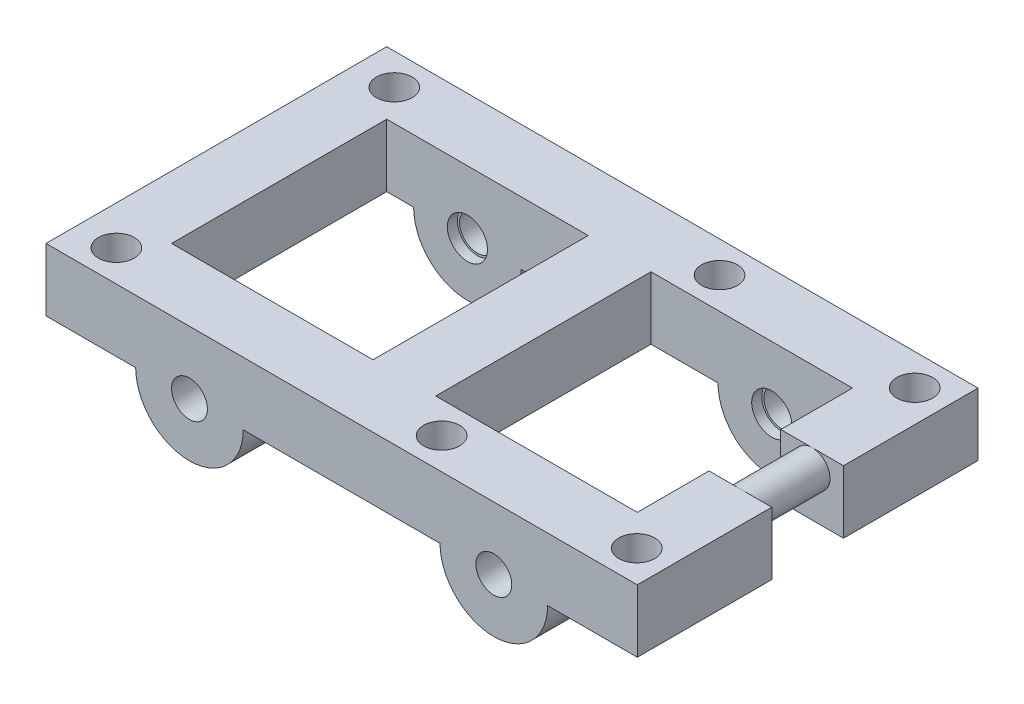
SolidWorks part; units mm, degrees
ref_plane "Front Plane" through (0, 0, 0) normal (0, 0, 1) x (1, 0, 0)
ref_plane "Top Plane" through (0, 0, 0) normal (0, 1, 0) x (1, 0, 0)
ref_plane "Right Plane" through (0, 0, 0) normal (1, 0, 0) x (0, 0, -1)
sketch "Sketch1" plane through (0, 0, 0) normal (0, 1, 0) x (1, 0, 0)
  line L0 (52.3438, 11.1125) -> (52.3438, 0) construction
  line L1 (0, 0) -> (104.6876, 0)
  line L2 (0, 0) -> (0, 60.325)
  line L3 (0, 60.325) -> (104.6876, 60.325)
  line L4 (104.6876, 0) -> (104.6876, 60.325)
  line L5 (11.1125, 11.1125) -> (46.7876, 11.1125)
  line L6 (11.1125, 11.1125) -> (11.1125, 49.2125)
  line L7 (11.1125, 49.2125) -> (46.7876, 49.2125)
  line L8 (93.5751, 11.1125) -> (93.5751, 49.2125)
  line L9 (93.5751, 30.1625) -> (104.6876, 30.1625) construction
  line L10 (46.7876, 30.1625) -> (57.9001, 30.1625) construction
  line L11 (57.9001, 11.1125) -> (93.5751, 11.1125)
  line L12 (46.7876, 49.2125) -> (46.7876, 11.1125)
  line L13 (0, 30.1625) -> (11.1125, 30.1625) construction
  line L14 (57.9001, 49.2125) -> (57.9001, 11.1125)
  line L15 (52.3438, 49.2125) -> (52.3438, 11.1125) construction
  line L16 (57.9001, 49.2125) -> (93.5751, 49.2125)
  point P22 (52.3438, 30.1625)
  dimension "D1" = 11.1125
  dimension "D2" = 11.1125
  dimension "D3" = 60.325
  dimension "D4" = 104.6876
extrude "Boss-Extrude1" add sketch "Sketch1" along normal blind 11.1125
sketch "Sketch2" plane through (0, 0, 0) normal (0, 0, 1) x (1, 0, 0)
  line L0 (0, 0) -> (104.6876, 0) construction
  line L1 (0, 11.1125) -> (0, 0) construction
  line L2 (104.6876, 11.1125) -> (104.6876, 0) construction
  line L3 (0, 11.1125) -> (104.6876, 11.1125) construction
  line L4 (0, 11.1125) -> (0, 0)
  line L5 (0, 0) -> (15.875, 0)
  line L6 (104.6876, 11.1125) -> (104.6876, 0)
  line L7 (0, 11.1125) -> (104.6876, 11.1125)
  line L8 (34.925, 0) -> (69.7626, 0)
  line L9 (88.8126, 0) -> (104.6876, 0)
  arc A0 (15.875, 0) -> (34.925, 0) centre (25.4, 0) ccw
  arc A1 (69.7626, 0) -> (88.8126, 0) centre (79.2876, 0) ccw
  point P7 (25.4, 0)
  point P10 (79.2876, 0)
  dimension "D3" = 19.05
  dimension "D1" = 25.4
  dimension "D2" = 25.4
extrude "Boss-Extrude32" add sketch "Sketch2" against normal up to surface (11.1125 mm away) up to face at (75.7376, 5.5562, -11.1125)
extrude "Boss-Extrude36" add sketch "Sketch2<11>" against normal up to surface (60.325 mm away) from vertex up to face at (52.3438, 5.5562, -60.325) starting at point (11.1125, 0, -49.2125)
sketch "Sketch2<11>" plane through (0, 0, 0) normal (0, 0, 1) x (1, 0, 0) same geometry as "Sketch2"
sketch "Sketch9" plane through (0, 11.1125, 0) normal (0, 1, 0) x (1, 0, 0)
  line L0 (93.5751, 11.1125) -> (93.5751, 49.2125) construction
  line L1 (93.5751, 36.5125) -> (104.6876, 36.5125)
  line L2 (93.5751, 36.5125) -> (93.5751, 23.8125)
  line L3 (93.5751, 23.8125) -> (104.6876, 23.8125)
  line L4 (104.6876, 36.5125) -> (104.6876, 23.8125)
  line L5 (104.6876, 0) -> (104.6876, 60.325) construction
  line L6 (57.9001, 49.2125) -> (57.9001, 11.1125) construction
  line L7 (57.9001, 30.1625) -> (93.5751, 30.1625) construction
  dimension "D1" = 12.7
extrude "Cut-Extrude1" cut sketch "Sketch9" against normal up to next
shell "Shell3" [suppressed] thickness 2.54
sketch "Sketch10" plane through (0, 0, -36.5125) normal (0, 0, 1) x (1, 0, 0)
  line L0 (99.1314, 11.1125) -> (99.1314, 0) construction
  line L3 (104.6876, 5.5563) -> (93.5751, 5.5562) construction
  line L4 (104.6876, 0) -> (104.6876, 11.1125) construction
  line L5 (93.5751, 0) -> (93.5751, 11.1125) construction
  line L6 (104.6876, 11.1125) -> (93.5751, 11.1125) construction
  line L7 (104.6876, 0) -> (93.5751, 0) construction
  circle A0 centre (99.1314, 7.9375) radius 3.175
  dimension "D1" = 6.35
extrude "Boss-Extrude37" add sketch "Sketch10" along normal up to next
ref_plane "Plane1" [suppressed] through (0, 3.81, 0) normal (0, -1, 0) x (-1, 0, 0)
sketch "Sketch16" [suppressed] plane through (0, 8.5725, 0) normal (0, -1, 0) x (1, 0, 0)
  line L0 (2.54, -2.54) -> (149.86, -2.54) construction
  line L1 (8.5725, -8.5725) -> (10.16, -8.5725)
  line L2 (8.5725, -8.5725) -> (8.5725, -2.54)
  line L3 (8.5725, -2.54) -> (10.16, -2.54)
  line L4 (10.16, -8.5725) -> (10.16, -2.54)
  line L5 (19.7485, -8.5725) -> (21.336, -8.5725)
  line L6 (19.7485, -8.5725) -> (19.7485, -2.54)
  line L7 (19.7485, -2.54) -> (21.336, -2.54)
  line L8 (21.336, -8.5725) -> (21.336, -2.54)
  line L9 (30.9245, -8.5725) -> (32.512, -8.5725)
  line L10 (30.9245, -8.5725) -> (30.9245, -2.54)
  line L11 (30.9245, -2.54) -> (32.512, -2.54)
  line L12 (32.512, -8.5725) -> (32.512, -2.54)
  line L13 (42.1005, -8.5725) -> (43.688, -8.5725)
  line L14 (42.1005, -8.5725) -> (42.1005, -2.54)
  line L15 (42.1005, -2.54) -> (43.688, -2.54)
  line L16 (43.688, -8.5725) -> (43.688, -2.54)
  line L17 (53.2765, -8.5725) -> (54.864, -8.5725)
  line L18 (53.2765, -8.5725) -> (53.2765, -2.54)
  line L19 (53.2765, -2.54) -> (54.864, -2.54)
  line L20 (54.864, -8.5725) -> (54.864, -2.54)
  line L21 (64.4525, -8.5725) -> (66.04, -8.5725)
  line L22 (64.4525, -8.5725) -> (64.4525, -2.54)
  line L23 (64.4525, -2.54) -> (66.04, -2.54)
  line L24 (66.04, -8.5725) -> (66.04, -2.54)
  line L25 (75.6285, -8.5725) -> (77.216, -8.5725)
  line L26 (75.6285, -8.5725) -> (75.6285, -2.54)
  line L27 (75.6285, -2.54) -> (77.216, -2.54)
  line L28 (77.216, -8.5725) -> (77.216, -2.54)
  line L29 (86.8045, -8.5725) -> (88.392, -8.5725)
  line L30 (86.8045, -8.5725) -> (86.8045, -2.54)
  line L31 (86.8045, -2.54) -> (88.392, -2.54)
  line L32 (88.392, -8.5725) -> (88.392, -2.54)
  line L33 (97.9805, -8.5725) -> (99.568, -8.5725)
  line L34 (97.9805, -8.5725) -> (97.9805, -2.54)
  line L35 (97.9805, -2.54) -> (99.568, -2.54)
  line L36 (99.568, -8.5725) -> (99.568, -2.54)
  line L37 (109.1565, -8.5725) -> (110.744, -8.5725)
  line L38 (109.1565, -8.5725) -> (109.1565, -2.54)
  line L39 (109.1565, -2.54) -> (110.744, -2.54)
  line L40 (110.744, -8.5725) -> (110.744, -2.54)
  line L41 (120.3325, -8.5725) -> (121.92, -8.5725)
  line L42 (120.3325, -8.5725) -> (120.3325, -2.54)
  line L43 (120.3325, -2.54) -> (121.92, -2.54)
  line L44 (121.92, -8.5725) -> (121.92, -2.54)
  line L45 (131.5085, -8.5725) -> (133.096, -8.5725)
  line L46 (131.5085, -8.5725) -> (131.5085, -2.54)
  line L47 (131.5085, -2.54) -> (133.096, -2.54)
  line L48 (133.096, -8.5725) -> (133.096, -2.54)
  line L49 (142.6845, -8.5725) -> (144.272, -8.5725)
  line L50 (142.6845, -8.5725) -> (142.6845, -2.54)
  line L51 (142.6845, -2.54) -> (144.272, -2.54)
  line L52 (144.272, -8.5725) -> (144.272, -2.54)
  dimension "D1" = 1.5875
extrude "Boss-Extrude38" [suppressed] add sketch "Sketch16" along normal blind 3.175
hole_wizard "#97 (0.0059) Diameter Hole1" positions "Sketch6" profile "Sketch5" hole size "#97" standard "ANSI Inch" end condition through all
sketch "Sketch6" plane through (0, 0, 0) normal (0, 0, 1) x (1, 0, 0)
  point P0 (25.4, 0)
  point P3 (79.2876, 0)
sketch "Sketch5" plane through (25.4, 0, 0) normal (1, 0, 0) x (0, -1, 0)
  line L0 (0, 0) -> (0, 60.325)
  line L1 (0, 60.325) -> (3.175, 60.325)
  line L2 (3.175, 60.325) -> (3.175, 0)
  line L5 (3.175, 0) -> (0, 0)
  line L11 (0, -6.35) -> (0, 107.95) construction
  dimension "Thru Hole Dia." = 6.35
  dimension "Thru Hole Depth" = 60.325
sketch "Sketch17" plane through (0, 0, -11.1125) normal (0, 0, -1) x (-1, 0, 0)
  circle A0 centre (-25.4, 0) radius 3.556
  circle A1 centre (-79.2876, 0) radius 3.556
  dimension "D1" = 7.112
extrude "Cut-Extrude2" cut sketch "Sketch17" against normal blind 1.778
sketch "Sketch18" plane through (0, 0, -49.2125) normal (0, 0, 1) x (1, 0, 0)
  circle A0 centre (25.4, 0) radius 3.556
  circle A1 centre (79.2876, 0) radius 3.556
  dimension "D1" = 7.112
extrude "Cut-Extrude3" cut sketch "Sketch18" against normal blind 1.778
sketch "Sketch19" plane through (0, 11.1125, 0) normal (0, 1, 0) x (1, 0, 0)
  line L0 (104.6876, 36.5125) -> (104.6876, 60.325) construction
  line L1 (104.6876, 60.325) -> (0, 60.325) construction
  line L2 (0, 0) -> (104.6876, 0) construction
  circle A0 centre (99.0361, 54.7687) radius 3.175
  circle A1 centre (64.487, 54.7687) radius 3.175
  circle A2 centre (-40.8112, 54.7687) radius 3.175
  circle A3 centre (99.0361, 5.5562) radius 3.175
  circle A4 centre (64.487, 5.5562) radius 3.175
  circle A5 centre (-40.8112, 5.5562) radius 3.175
  dimension "D6" = 6.35
  dimension "D1" = 5.6515
  dimension "D2" = 40.2006
  dimension "D3" = 145.4988
  dimension "D4" = 5.5562
  dimension "D5" = 5.5562
extrude "Cut-Extrude4" cut sketch "Sketch19" against normal blind 5.842
sketch "Sketch20" plane through (0, 5.2705, 0) normal (0, 1, 0) x (1, 0, 0)
  line L0 (0, 0) -> (15.875, 0) construction
  line L1 (0, 60.325) -> (0, 0) construction
  line L2 (104.6876, 0) -> (104.6876, 23.8125) construction
  line L3 (15.875, 60.325) -> (0, 60.325) construction
  circle A0 centre (99.0361, 54.7687) radius 3.556
  circle A1 centre (64.487, 54.7687) radius 3.556
  circle A2 centre (6.9012, 54.7687) radius 3.556
  circle A3 centre (6.9012, 5.5562) radius 3.556
  circle A4 centre (64.487, 5.5562) radius 3.556
  circle A5 centre (99.0361, 5.5562) radius 3.556
  dimension "D1" = 7.112
  dimension "D2" = 5.5562
  dimension "D3" = 6.9012
  dimension "D4" = 5.6515
  dimension "D5" = 40.2006
  dimension "D6" = 5.5562
extrude "Cut-Extrude7" cut sketch "Sketch20" against normal through all both and the other way through all
sketch "Sketch24" plane through (0, 11.1125, 0) normal (0, 1, 0) x (1, 0, 0)
  circle A0 centre (6.9012, 54.7687) radius 3.175
  circle A1 centre (64.487, 54.7687) radius 3.175
  circle A2 centre (99.0361, 54.7687) radius 3.175
  circle A3 centre (99.0361, 5.5562) radius 3.175
  circle A4 centre (64.487, 5.5562) radius 3.175
  circle A5 centre (6.9012, 5.5562) radius 3.175
  circle A6 centre (6.9012, 5.5562) radius 3.556 construction
  circle A7 centre (64.487, 5.5562) radius 3.556 construction
  circle A8 centre (64.487, 5.5562) radius 3.556
  circle A9 centre (6.9012, 54.7687) radius 3.556
  circle A10 centre (64.487, 54.7687) radius 3.556
  circle A11 centre (99.0361, 54.7687) radius 3.556
  circle A12 centre (99.0361, 5.5562) radius 3.556
  circle A13 centre (6.9012, 5.5562) radius 3.556
  circle A14 centre (6.9012, 54.7687) radius 3.556 construction
  dimension "D1" = 6.35
extrude "Boss-Extrude40" add sketch "Sketch24" against normal blind 5.842
